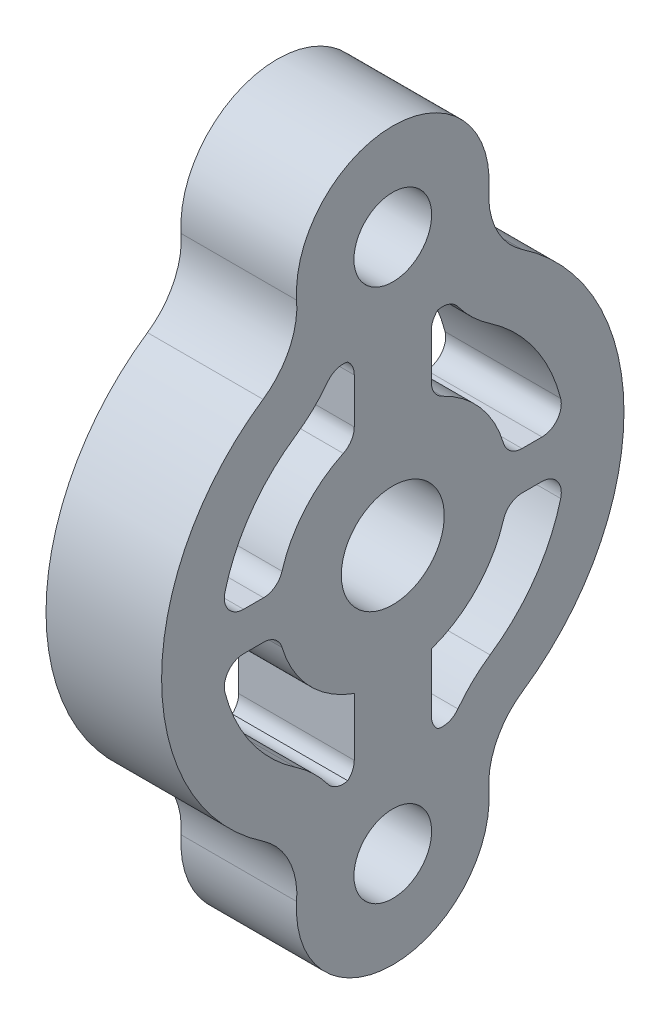
SolidWorks part; units mm, degrees
ref_plane "Front Plane" through (0, 0, 0) normal (0, 0, 1) x (1, 0, 0)
ref_plane "Top Plane" through (0, 0, 0) normal (0, 1, 0) x (1, 0, 0)
ref_plane "Right Plane" through (0, 0, 0) normal (1, 0, 0) x (0, 0, -1)
sketch "Sketch1" plane through (0, 0, 0) normal (1, 0, 0) x (0, 0, -1)
  line L0 (0, -11) -> (0, 11) construction
  circle A0 centre (0, 0) radius 2.1209
  circle A1 centre (0, 11) radius 1.6002
  circle A4 centre (0, -11) radius 1.6002
  arc A5 (-3.9595, 10.7287) -> (3.9595, 10.7287) centre (0, 11) cw
  arc A6 (-3.9595, -10.7287) -> (3.9595, -10.7287) centre (0, -11) ccw
  arc A7 (5.3453, -7.8838) -> (5.3453, 7.8838) centre (0, 0) ccw
  arc A8 (-5.3453, 7.8838) -> (-5.3453, -7.8838) centre (0, 0) ccw
  arc A9 (-5.3453, -7.8838) -> (-3.9595, -10.7287) centre (-7.127, -10.5117) cw
  arc A10 (5.3453, -7.8838) -> (3.9595, -10.7287) centre (7.127, -10.5117) ccw
  arc A11 (5.3453, 7.8838) -> (3.9595, 10.7287) centre (7.127, 10.5117) cw
  arc A12 (-5.3453, 7.8838) -> (-3.9595, 10.7287) centre (-7.127, 10.5117) ccw
  point P2 (0, 0)
  point P20 (-6.6687, -6.8011)
  dimension "D2" = 4.2418
  dimension "D3" = 11
  dimension "D1" = 7.9375
  dimension "D4" = 3.2004
  dimension "D5" = 3.2004
  dimension "D6" = 19.05
  dimension "D7" = 3.175
extrude "Boss-Extrude1" add sketch "Sketch1" along normal blind 4.7625
sketch "Sketch2" plane through (4.7625, 0, 0) normal (1, 0, 0) x (0, 0, -1)
  line L0 (-1.5875, -7.3626) -> (-1.5875, -4.4901)
  line L1 (1.5875, -7.3626) -> (1.5875, -4.4901)
  line L2 (-4.6959, -0.7938) -> (-7.0995, -0.7938)
  line L3 (-7.0995, 0.7938) -> (-4.6959, 0.7938)
  line L4 (-1.5875, 7.3626) -> (-1.5875, 4.4901)
  line L5 (1.5875, 4.4901) -> (1.5875, 7.3626)
  line L6 (4.6959, 0.7938) -> (7.0995, 0.7938)
  line L7 (4.6959, -0.7938) -> (7.0995, -0.7938)
  arc A8 (3.9595, 10.7287) -> (-3.9595, 10.7287) centre (0, 11) ccw construction
  arc A9 (-2.2977, 7.764) -> (-1.5875, 7.3626) centre (0, 11) ccw
  arc A10 (-3.9595, -10.7287) -> (3.9595, -10.7287) centre (0, -11) ccw construction
  arc A11 (2.2977, -7.764) -> (1.5875, -7.3626) centre (0, -11) ccw
  arc A12 (1.5875, -4.4901) -> (4.6959, -0.7938) centre (0, 0) ccw
  arc A13 (-1.5875, -7.3626) -> (-2.2977, -7.764) centre (0, -11) ccw
  arc A14 (-4.6959, -0.7938) -> (-1.5875, -4.4901) centre (0, 0) ccw
  arc A15 (-7.0995, -0.7938) -> (-4.009, -5.9128) centre (0, 0) ccw
  arc A16 (-4.009, 5.9128) -> (-4.009, -5.9128) centre (0, 0) ccw
  arc A17 (-1.5838, -10.8915) -> (-4.009, -5.9128) centre (-7.127, -10.5117) ccw
  arc A18 (-1.5838, -10.8915) -> (1.5838, -10.8915) centre (0, -11) ccw
  arc A19 (4.009, -5.9128) -> (1.5838, -10.8915) centre (7.127, -10.5117) ccw
  arc A20 (4.009, -5.9128) -> (4.009, 5.9128) centre (0, 0) ccw
  arc A21 (1.5838, 10.8915) -> (4.009, 5.9128) centre (7.127, 10.5117) ccw
  arc A22 (1.5838, 10.8915) -> (-1.5838, 10.8915) centre (0, 11) ccw
  arc A23 (-4.009, 5.9128) -> (-1.5838, 10.8915) centre (-7.127, 10.5117) ccw
  arc A24 (-4.009, 5.9128) -> (-7.0995, 0.7938) centre (0, 0) ccw
  arc A25 (-2.2977, -7.764) -> (-4.009, -5.9128) centre (-7.127, -10.5117) ccw
  arc A27 (4.009, -5.9128) -> (2.2977, -7.764) centre (7.127, -10.5117) ccw
  arc A28 (4.009, -5.9128) -> (7.0995, -0.7938) centre (0, 0) ccw
  arc A29 (2.2977, 7.764) -> (4.009, 5.9128) centre (7.127, 10.5117) ccw
  arc A31 (-4.009, 5.9128) -> (-2.2977, 7.764) centre (-7.127, 10.5117) ccw
  arc A32 (7.0995, 0.7938) -> (4.009, 5.9128) centre (0, 0) ccw
  arc A33 (4.6959, 0.7938) -> (1.5875, 4.4901) centre (0, 0) ccw
  arc A34 (1.5875, 7.3626) -> (2.2977, 7.764) centre (0, 11) ccw
  arc A35 (-1.5875, 4.4901) -> (-4.6959, 0.7938) centre (0, 0) ccw
  dimension "D2" = 9.525
  dimension "D3" = 3.175
  dimension "D4" = 1.5875
  dimension "D1" = 2.3813
extrude "Cut-Extrude1" cut sketch "Sketch2" against normal through all
fillet "Fillet1" radius 0.7937 18 edges at (2.3813, -0.7938, -4.6959) (2.3813, -0.7938, -7.0995) (2.3813, 0.7938, -7.0995) (2.3813, 0.7938, -4.6959) (2.3813, 4.4901, -1.5875) (2.3813, 7.764, -2.2977) (2.3813, 7.3626, -1.5875) (2.3813, 4.4901, 1.5875) (2.3813, 7.3626, 1.5875) (2.3813, 7.764, 2.2977) (2.3813, 0.7938, 4.6959) (2.3813, -0.7938, 4.6959) (2.3813, 0.7938, 7.0995) (2.3813, -0.7938, 7.0995) (2.3813, -7.764, 2.2977) (2.3813, -7.3626, 1.5875) (2.3813, -7.3626, -1.5875) (2.3813, -7.764, -2.2977)
